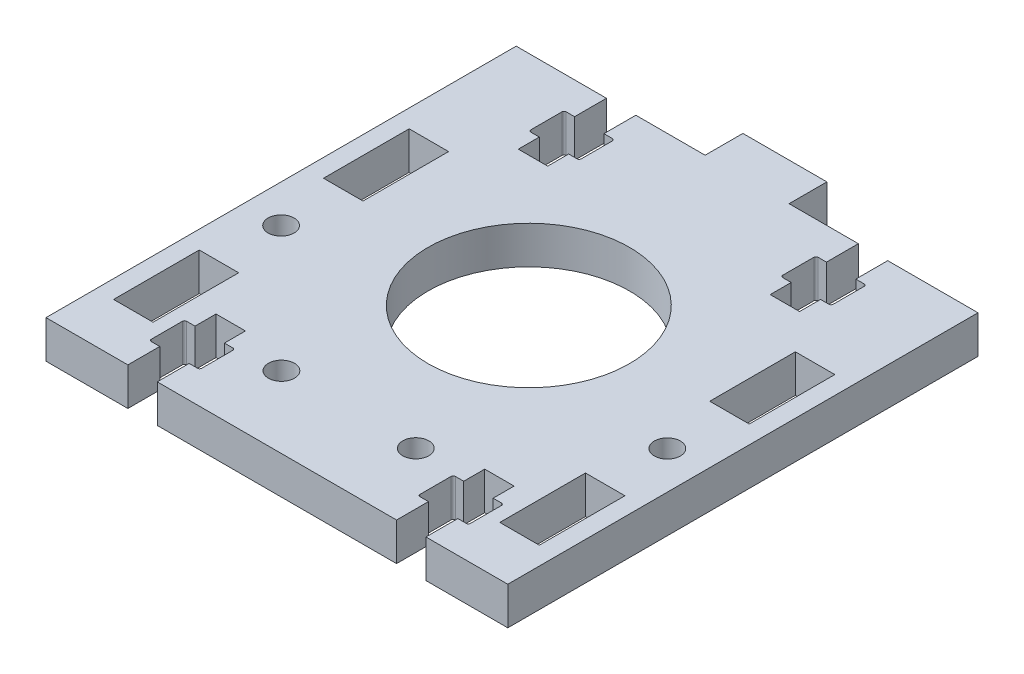
SolidWorks part; units mm, degrees
ref_plane "Front Plane" through (0, 0, 0) normal (0, 0, 1) x (1, 0, 0)
ref_plane "Top Plane" through (0, 0, 0) normal (0, 1, 0) x (1, 0, 0)
ref_plane "Right Plane" through (0, 0, 0) normal (1, 0, 0) x (0, 0, -1)
sketch "Sketch1" plane through (0, 0, 0) normal (0, 1, 0) x (1, 0, 0)
  line L1 (-27.5, 28) -> (27.5, 28)
  line L2 (-27.5, 28) -> (-27.5, -28)
  line L3 (-27.5, -28) -> (27.5, -28)
  line L4 (27.5, 28) -> (27.5, -28)
  line L5 (-27.5, 28) -> (27.5, -28) construction
  line L6 (-27.5, -28) -> (27.5, 28) construction
  point P0 (0, 0)
  dimension "D1" = 55
  dimension "D2" = 56
extrude "MainShape" add sketch "Sketch1" along normal blind 4.5
sketch "Sketch2" plane through (0, 4.5, 0) normal (0, 1, 0) x (1, 0, 0)
  line L0 (0, -28) -> (0, 28) construction
  line L1 (-27.5, -28) -> (27.5, -28) construction
  line L2 (27.5, 28) -> (-27.5, 28) construction
  line L4 (-5, 32.5) -> (5, 32.5)
  line L5 (-5, 32.5) -> (-5, 23.5)
  line L6 (-5, 23.5) -> (5, 23.5)
  line L7 (5, 32.5) -> (5, 23.5)
  line L8 (-5, 32.5) -> (5, 23.5) construction
  line L9 (-5, 23.5) -> (5, 32.5) construction
  dimension "D2" = 4.5
extrude "Tab1" add sketch "Sketch2" against normal through all
sketch "Sketch4" plane through (0, 4.5, 0) normal (0, 1, 0) x (1, 0, 0)
  line L0 (0, 32.5) -> (0, -28) construction
  line L1 (5, 32.5) -> (-5, 32.5) construction
  line L2 (-27.5, -28) -> (27.5, -28) construction
  line L3 (-15, 28) -> (-15, 17.5) construction
  line L4 (-5, 28) -> (-27.5, 28) construction
  line L5 (-13.25, 17.5) -> (-16.75, 17.5) construction
  line L6 (-16.75, 17.5) -> (-16.75, 28) construction
  line L7 (-13.25, 17.5) -> (-16.75, 17.5)
  line L8 (-16.75, 17.5) -> (-16.75, 20)
  line L9 (-16.75, 20) -> (-17.75, 20)
  line L10 (-18, 20.25) -> (-18, 23.95)
  line L11 (-17.75, 24.2) -> (-16.75, 24.2)
  line L12 (-16.75, 24.2) -> (-16.75, 28)
  line L13 (-16.75, 28) -> (-13.25, 28)
  line L14 (-13.25, 17.5) -> (-13.25, 28) construction
  line L15 (-13.25, 24.2) -> (-13.25, 28)
  line L16 (-12.25, 24.2) -> (-13.25, 24.2)
  line L17 (-12, 20.25) -> (-12, 23.95)
  line L18 (-13.25, 20) -> (-12.25, 20)
  line L19 (-13.25, 17.5) -> (-13.25, 20)
  line L20 (13.25, 17.5) -> (13.25, 28) construction
  line L21 (16.75, 17.5) -> (16.75, 28) construction
  line L22 (13.25, 17.5) -> (16.75, 17.5) construction
  line L23 (15, 28) -> (15, 17.5) construction
  line L24 (13.25, 17.5) -> (13.25, 20)
  line L25 (13.25, 20) -> (12.25, 20)
  line L26 (12, 20.25) -> (12, 23.95)
  line L27 (12.25, 24.2) -> (13.25, 24.2)
  line L28 (13.25, 24.2) -> (13.25, 28)
  line L29 (16.75, 28) -> (13.25, 28)
  line L30 (16.75, 24.2) -> (16.75, 28)
  line L31 (17.75, 24.2) -> (16.75, 24.2)
  line L32 (18, 20.25) -> (18, 23.95)
  line L33 (16.75, 20) -> (17.75, 20)
  line L34 (16.75, 17.5) -> (16.75, 20)
  line L35 (13.25, 17.5) -> (16.75, 17.5)
  arc A0 (-17.75, 20) -> (-18, 20.25) centre (-17.75, 20.25) cw
  arc A1 (-12, 20.25) -> (-12.25, 20) centre (-12.25, 20.25) cw
  arc A2 (-12.25, 24.2) -> (-12, 23.95) centre (-12.25, 23.95) cw
  arc A3 (-18, 23.95) -> (-17.75, 24.2) centre (-17.75, 23.95) cw
  arc A4 (18, 23.95) -> (17.75, 24.2) centre (17.75, 23.95) ccw
  arc A5 (12.25, 24.2) -> (12, 23.95) centre (12.25, 23.95) ccw
  arc A6 (12, 20.25) -> (12.25, 20) centre (12.25, 20.25) ccw
  arc A7 (17.75, 20) -> (18, 20.25) centre (17.75, 20.25) ccw
  point P24 (-18, 20)
  point P27 (-12, 20)
  point P30 (-12, 24.2)
  point P33 (-18, 24.2)
  point P56 (18, 24.2)
  point P57 (12, 24.2)
  point P58 (12, 20)
  point P59 (18, 20)
  dimension "D7" = 0.25
  dimension "D1" = 10.5
  dimension "D2" = 1.75
  dimension "D3" = 4.2
  dimension "D4" = 3
  dimension "D5" = 8
  dimension "D6" = 15
extrude "Cut-Extrude2" cut sketch "Sketch4" against normal through all
sketch "Sketch5" plane through (0, 4.5, 0) normal (0, 1, 0) x (1, 0, 0)
  line L0 (0, -28) -> (0, 32.5) construction
  line L1 (-27.5, -28) -> (27.5, -28) construction
  line L2 (5, 32.5) -> (-5, 32.5) construction
  line L3 (23, 28) -> (23, -28) construction
  line L4 (27.5, 28) -> (16.75, 28) construction
  line L5 (-23, 28) -> (-23, -28) construction
  line L6 (20.65, 13.1) -> (25.35, 13.1)
  line L7 (20.65, 13.1) -> (20.65, 2.9)
  line L8 (20.65, 2.9) -> (25.35, 2.9)
  line L9 (25.35, 13.1) -> (25.35, 2.9)
  line L10 (20.65, 13.1) -> (25.35, 2.9) construction
  line L11 (20.65, 2.9) -> (25.35, 13.1) construction
  line L12 (-20.65, 2.9) -> (-25.35, 13.1) construction
  line L13 (-20.65, 13.1) -> (-25.35, 2.9) construction
  line L14 (-25.35, 13.1) -> (-25.35, 2.9)
  line L15 (-20.65, 2.9) -> (-25.35, 2.9)
  line L16 (-20.65, 13.1) -> (-20.65, 2.9)
  line L17 (-20.65, 13.1) -> (-25.35, 13.1)
  line L18 (-27.5, -4.5) -> (27.5, -4.5) construction
  line L19 (-27.5, 28) -> (-27.5, -28) construction
  line L20 (27.5, -28) -> (27.5, 28) construction
  line L21 (-20.65, -22.1) -> (-25.35, -11.9) construction
  line L22 (-20.65, -11.9) -> (-25.35, -22.1) construction
  line L23 (20.65, -11.9) -> (25.35, -22.1) construction
  line L24 (20.65, -22.1) -> (25.35, -11.9) construction
  line L25 (-20.65, -22.1) -> (-25.35, -22.1)
  line L26 (-20.65, -22.1) -> (-20.65, -11.9)
  line L27 (-20.65, -11.9) -> (-25.35, -11.9)
  line L28 (-25.35, -22.1) -> (-25.35, -11.9)
  line L29 (25.35, -22.1) -> (25.35, -11.9)
  line L30 (20.65, -11.9) -> (25.35, -11.9)
  line L31 (20.65, -22.1) -> (20.65, -11.9)
  line L32 (20.65, -22.1) -> (25.35, -22.1)
  line L33 (-20.65, 13.1) -> (-25.35, 2.9) construction
  circle A0 centre (23, -4.5) radius 1.55
  circle A1 centre (-23, -4.5) radius 1.55
  point P10 (23, 8)
  point P21 (-23, 8)
  point P36 (-23, -17)
  point P37 (23, -17)
  dimension "D6" = 3.1
  dimension "D1" = 23
  dimension "D2" = 10.2
  dimension "D3" = 4.7
  dimension "D4" = 20
  dimension "D5" = 25
extrude "Cut-Extrude3" cut sketch "Sketch5" against normal through all
sketch "Sketch6" plane through (0, 4.5, 0) normal (0, 1, 0) x (1, 0, 0)
  line L0 (0, -28) -> (0, 28) construction
  line L1 (5, 32.5) -> (-5, 32.5) construction
  line L3 (-27.5, 2) -> (27.5, 2) construction
  line L4 (-27.5, 28) -> (-27.5, -28) construction
  line L5 (27.5, -28) -> (27.5, 28) construction
  line L6 (27.5, 28) -> (16.75, 28) construction
  line L7 (-27.5, -28) -> (27.5, -28) construction
  line L9 (-27.5, 28) -> (27.5, 28) construction
  circle A0 centre (0, 2) radius 12
  point P4 (0, 32.5)
  dimension "D1" = 24
  dimension "D2" = 26
extrude "Cut-Extrude4" cut sketch "Sketch6" against normal through all
sketch "Sketch7" plane through (0, 4.5, 0) normal (0, 1, 0) x (1, 0, 0)
  line L0 (0, 2) -> (0, -28) construction
  line L3 (-27.5, -28) -> (27.5, -28) construction
  line L4 (8, -19.46) -> (-8, -19.46) construction
  circle A1 centre (-8, -19.46) radius 1.55
  circle A2 centre (8, -19.46) radius 1.55
  point P8 (0, -19.46)
  dimension "D1" = 3.1
  dimension "D2" = 8
  dimension "D3" = 21.46
extrude "Cut-Extrude5" [suppressed] cut sketch "Sketch7" against normal through all
sketch "Sketch8" plane through (0, 4.5, 0) normal (0, 1, 0) x (1, 0, 0)
  line L0 (-12, 2) -> (12, 2) construction
  line L1 (0, 2) -> (0, -19.46) construction
  line L2 (8, -19.46) -> (-8, -19.46) construction
  line L3 (0, -10) -> (0, 14) construction
  circle A0 centre (-8, -19.46) radius 1.55
  circle A1 centre (0, 2) radius 12 construction
  circle A2 centre (8, -19.46) radius 1.55
  dimension "D2" = 8
  dimension "D3" = 3.1
  dimension "D1" = 90
  dimension "D4" = 21.46
extrude "Cut-Extrude6" cut sketch "Sketch8" against normal through all
sketch "Sketch9" plane through (0, 4.5, 0) normal (0, 1, 0) x (1, 0, 0)
  line L0 (0, -28) -> (0, 32.5) construction
  line L1 (-27.5, -28) -> (27.5, -28) construction
  line L2 (5, 32.5) -> (-5, 32.5) construction
  line L3 (16, -28) -> (16, -17.5) construction
  line L4 (14.25, -17.5) -> (17.75, -17.5) construction
  line L5 (17.75, -17.5) -> (17.75, -28) construction
  line L6 (17.75, -28) -> (17.75, -24.2)
  line L7 (17.75, -24.2) -> (18.75, -24.2)
  line L8 (19, -23.95) -> (19, -20.25)
  line L9 (18.75, -20) -> (17.75, -20)
  line L10 (17.75, -20) -> (17.75, -17.5)
  line L11 (17.75, -17.5) -> (14.25, -17.5)
  line L12 (17.75, -28) -> (14.25, -28)
  line L13 (14.25, -17.5) -> (14.25, -28) construction
  line L14 (14.25, -20) -> (14.25, -17.5)
  line L15 (13.25, -20) -> (14.25, -20)
  line L16 (13, -23.95) -> (13, -20.25)
  line L17 (14.25, -24.2) -> (13.25, -24.2)
  line L18 (14.25, -28) -> (14.25, -24.2)
  line L19 (-14.25, -17.5) -> (-14.25, -28) construction
  line L20 (-17.75, -17.5) -> (-17.75, -28) construction
  line L21 (-14.25, -17.5) -> (-17.75, -17.5) construction
  line L22 (-16, -28) -> (-16, -17.5) construction
  line L23 (-14.25, -28) -> (-14.25, -24.2)
  line L24 (-14.25, -24.2) -> (-13.25, -24.2)
  line L25 (-13, -23.95) -> (-13, -20.25)
  line L26 (-13.25, -20) -> (-14.25, -20)
  line L27 (-14.25, -20) -> (-14.25, -17.5)
  line L28 (-17.75, -28) -> (-14.25, -28)
  line L29 (-17.75, -17.5) -> (-14.25, -17.5)
  line L30 (-17.75, -20) -> (-17.75, -17.5)
  line L31 (-18.75, -20) -> (-17.75, -20)
  line L32 (-19, -23.95) -> (-19, -20.25)
  line L33 (-17.75, -24.2) -> (-18.75, -24.2)
  line L34 (-17.75, -28) -> (-17.75, -24.2)
  arc A0 (18.75, -24.2) -> (19, -23.95) centre (18.75, -23.95) ccw
  arc A1 (19, -20.25) -> (18.75, -20) centre (18.75, -20.25) ccw
  arc A2 (13, -20.25) -> (13.25, -20) centre (13.25, -20.25) cw
  arc A3 (13.25, -24.2) -> (13, -23.95) centre (13.25, -23.95) cw
  arc A4 (-13.25, -24.2) -> (-13, -23.95) centre (-13.25, -23.95) ccw
  arc A5 (-13, -20.25) -> (-13.25, -20) centre (-13.25, -20.25) ccw
  arc A6 (-19, -20.25) -> (-18.75, -20) centre (-18.75, -20.25) cw
  arc A7 (-18.75, -24.2) -> (-19, -23.95) centre (-18.75, -23.95) cw
  point P16 (19, -24.2)
  point P19 (19, -20)
  point P30 (13, -20)
  point P31 (13, -24.2)
  point P54 (-13, -24.2)
  point P55 (-13, -20)
  point P56 (-19, -20)
  point P57 (-19, -24.2)
  dimension "D7" = 0.25
  dimension "D1" = 10.5
  dimension "D2" = 1.75
  dimension "D3" = 8
  dimension "D4" = 4.2
  dimension "D5" = 3
  dimension "D6" = 16
extrude "Cut-Extrude7" cut sketch "Sketch9" against normal through all
sketch "Sketch10" plane through (0, 0, 28) normal (0, 0, 1) x (1, 0, 0)
  line L0 (-27.5, 2.25) -> (27.5, 2.25) construction
  line L1 (-27.5, 4.5) -> (-27.5, 0) construction
  line L2 (27.5, 4.5) -> (27.5, 0) construction
  line L3 (-16, 4.5) -> (-16, 0) construction
  line L4 (-14.25, 4.5) -> (-17.75, 4.5) construction
  line L5 (16, 4.5) -> (16, 0) construction
  line L6 (17.75, 4.5) -> (14.25, 4.5) construction
  line L7 (17.75, 0) -> (14.25, 0) construction
  line L8 (-14.25, 0) -> (-17.75, 0) construction
  circle A0 centre (-16, 2.25) radius 1.6
  circle A1 centre (16, 2.25) radius 1.6
  dimension "D1" = 3.2
  dimension "D2" = 3.2
equation "\"X-ROD-SPACING\"=45"
equation "\"Y-ROD-SPACING\"=75"
equation "\"Z-ROD-SPACING\"=17.5"
equation "\"Y-BED-OFFSET\"=2"
equation "\"Y-BED-ROD-INSET\"=3.5"
equation "\"Y-BED-SCREW-SPACING\"=209"
equation "\"Y-BED-SCREW-CUTOUT-SLOT-HEIGHT\"=1"
equation "\"T-SLOT-NUT-FILLET-RADIUS\"=0.25"
equation "\"T-SLOT-SCREW-SHAFT-RADIUS\"=1.75"
equation "\"T-SLOT-SCREW-SHAFT-CUTOUT-LENGTH\"=10.5"
equation "\"T-SLOT-NUT-DEPTH\"=4.2"
equation "\"T-SLOT-NUT-WIDTH\"=3"
equation "\"T-SLOT-NUT-END-DISTANCE\"=8"
equation "\"ACRYLIC-THICKNESS\"=10"
equation "\"ACRYLIC-THICKNESS2\"=4.5"
equation "\"ACRYLIC-TAB-CUTOUT-SIZE\"=\"ACRYLIC-THICKNESS\"+\"ACRYLIC-TAB-TOLERANCE\"*2"
equation "\"ACRYLIC-TAB-WIDTH\"=\"ACRYLIC-THICKNESS\""
equation "\"ACRYLIC-M3-HOLE\"=3.1"
equation "\"SMOOTHROD-CAP-SCREW-DISTANCE\"=20"
equation "\"FRAME-WIDTH-INNER\"=370"
equation "\"NEMA17-HOLE-SPACING\"=31"
equation "\"NEMA17-CENTRAL-CUTOUT\"=22.5"
equation "\"Z-BRACKET-REACH\"=55"
equation "\"Z-ROD-INSET\"=16"
equation "\"TOP-BRACKET-SPACING\"=40"
equation "\"SMOOTHROD-X-LENGTH\"=350"
equation "\"SMOOTHROD-Y-LENGTH\"=350"
equation "\"SMOOTHROD-Z-LENGTH\"=350"
equation "\"SMOOTHROD-TIGHTENING-HEADROOM\"=1"
equation "\"LEADSCREW-Z-LENGTH\"=300"
equation "\"SCREW-LENGTH-FRAME\"=\"ACRYLIC-THICKNESS\" + 10"
equation "\"SCREW-LENGTH-MOTOR\"=\"ACRYLIC-THICKNESS\" + 5"
equation "\"SCREW-LENGTH-EXTRUDER\"=28"
equation "\"SCREW-HEAD-RADIUS\"=6"
equation "\"PRINTED-X-SMOOTHROD-DIAMETER\"=8.2"
equation "\"PRINTED-X-SMOOTHROD-CUTOUT\"=10"
equation "\"PRINTED-X-BASE-HEIGHT\"=10"
equation "\"PRINTED-LM8UU-CUTOUT-SIZE\"=15.25"
equation "\"PRINTED-LM8UU-CUTOUT-LENGTH\"=24.5"
equation "\"PRINTED-X-IDLER-HEIGHT\"=16"
equation "\"PSU-MOUNTING-WIDTH\"=95"
equation "\"PSU-MOUNTING-HEIGHT\"=177"
equation "\"Y-BELT-TO-ROD-DISTANCE\"=20"
equation "\"SPOOL-HOLDER-ROD-SPACING\"=150"
equation "\"ACRYLIC-X-CARRIAGE-WIDTH\"=55"
equation "\"ACRYLIC-X-CARRIAGE-HEIGHT\"=75"
equation "\"ACRYLIC-X-CARRIAGE-SCREW-SPACING-X\"=15"
equation "\"ACRYLIC-X-CARRIAGE-SCREW-SPACING-Y\"=33"
equation "\"ACRYLIC-X-CARRIAGE-CENTER-TAB-SPACING\"=14"
equation "\"D1@Sketch1\"=\"ACRYLIC-X-CARRIAGE-WIDTH\""
equation "\"D1@MainShape\" = \"ACRYLIC-THICKNESS2\""
equation "\"D1@Sketch2\"=\"ACRYLIC-TAB-WIDTH\""
equation "\"D2@Sketch2\"=\"ACRYLIC-THICKNESS2\""
equation "\"D1@Sketch4\"=\"T-SLOT-SCREW-SHAFT-CUTOUT-LENGTH\""
equation "\"D2@Sketch4\"=\"T-SLOT-SCREW-SHAFT-RADIUS\""
equation "\"D3@Sketch4\"=\"T-SLOT-NUT-DEPTH\""
equation "\"D4@Sketch4\"=\"T-SLOT-NUT-WIDTH\""
equation "\"D5@Sketch4\"=\"T-SLOT-NUT-END-DISTANCE\""
equation "\"D6@Sketch4\"=\"ACRYLIC-X-CARRIAGE-SCREW-SPACING-X\""
equation "\"D7@Sketch4\"=\"T-SLOT-NUT-FILLET-RADIUS\""
equation "\"ACRYLIC-X-CARRIAGE-EXTRUDER-SHELF-DEPTH\"=\"ACRYLIC-X-CARRIAGE-EXTRUDER-OFFSET\" + 30"
equation "\"D2@Sketch1\"=\"ACRYLIC-X-CARRIAGE-EXTRUDER-SHELF-DEPTH\""
equation "\"ACRYLIC-X-CARRIAGE-LM8UU-CUTOUT-WIDTH\"=24.25"
equation "\"ACRYLIC-X-CARRIAGE-EXTRUDER-BRACE-SPACING\"=23"
equation "\"ACRYLIC-X-CARRIAGE-EXTRUDER-BRACE-TAB-OFFSET\"=20"
equation "\"ACRYLIC-X-CARRIAGE-EXTRUDER-BRACE-HEIGHT\"=35"
equation "\"ACRYLIC-X-CARRIAGE-EXTRUDER-BRACE-SCREW-SPACING\"=22"
equation "\"D1@Sketch5\"=\"ACRYLIC-X-CARRIAGE-EXTRUDER-BRACE-SPACING\""
equation "\"D2@Sketch5\"=\"ACRYLIC-TAB-CUTOUT-SIZE\""
equation "\"D3@Sketch5\"=\"ACRYLIC-THICKNESS2\"+\"ACRYLIC-TAB-TOLERANCE\"*2"
equation "\"D4@Sketch5\"=\"ACRYLIC-X-CARRIAGE-EXTRUDER-BRACE-TAB-OFFSET\""
equation "\"D1@Sketch7\"=\"ACRYLIC-M3-HOLE\""
equation "\"D3@Sketch8\"=\"ACRYLIC-M3-HOLE\""
equation "\"ACRYLIC-X-CARRIAGE-EXTRUDER-ANGLE\"=90"
equation "\"D1@Sketch8\"=\"ACRYLIC-X-CARRIAGE-EXTRUDER-ANGLE\""
equation "\"ACRYLIC-X-CARRIAGE-EXTRUDER-OFFSET\"=26"
equation "\"D2@Sketch6\"=\"ACRYLIC-X-CARRIAGE-EXTRUDER-OFFSET\""
equation "\"D6@Sketch5\"=\"ACRYLIC-M3-HOLE\""
equation "\"D1@Sketch9\"=\"T-SLOT-SCREW-SHAFT-CUTOUT-LENGTH\""
equation "\"D2@Sketch9\"=\"T-SLOT-SCREW-SHAFT-RADIUS\""
equation "\"D3@Sketch9\"=\"T-SLOT-NUT-END-DISTANCE\""
equation "\"D4@Sketch9\"=\"T-SLOT-NUT-DEPTH\""
equation "\"D5@Sketch9\"=\"T-SLOT-NUT-WIDTH\""
equation "\"D7@Sketch9\"=\"T-SLOT-NUT-FILLET-RADIUS\""
equation "\"ACRYLIC-TAB-TOLERANCE\"=.1"
